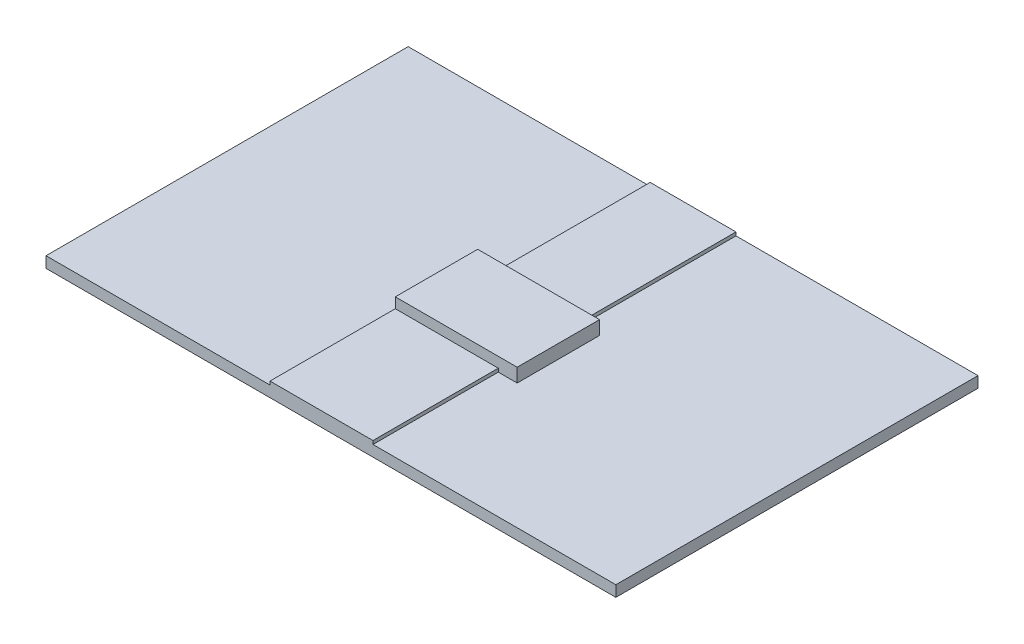
SolidWorks part; units mm, degrees
ref_plane "Front Plane" through (0, 0, 0) normal (0, 0, 1) x (1, 0, 0)
ref_plane "Top Plane" through (0, 0, 0) normal (0, 1, 0) x (1, 0, 0)
ref_plane "Right Plane" through (0, 0, 0) normal (1, 0, 0) x (0, 0, -1)
sketch "Sketch1" plane through (0, 0, 0) normal (0, 1, 0) x (1, 0, 0)
  line L1 (-83, 52.75) -> (83, 52.75)
  line L2 (-83, 52.75) -> (-83, -52.75)
  line L3 (-83, -52.75) -> (83, -52.75)
  line L4 (83, 52.75) -> (83, -52.75)
  line L5 (-83, 52.75) -> (83, -52.75) construction
  line L6 (-83, -52.75) -> (83, 52.75) construction
  line L7 (-17.75, -16.25) -> (17.75, -16.25)
  line L8 (-17.75, -16.25) -> (-17.75, 7.75)
  line L9 (-17.75, 7.75) -> (17.75, 7.75)
  line L10 (17.75, -16.25) -> (17.75, 7.75)
  line L11 (-17.75, -16.25) -> (17.75, 7.75) construction
  line L12 (-17.75, 7.75) -> (17.75, -16.25) construction
  line L13 (-17.75, -16.25) -> (12.25, -16.25)
  line L14 (-17.75, -16.25) -> (-17.75, -52.75)
  line L15 (-17.75, -52.75) -> (12.25, -52.75)
  line L16 (12.25, -16.25) -> (12.25, -52.75)
  line L17 (12.5, 7.75) -> (-12.5, 7.75)
  line L18 (12.5, 7.75) -> (12.5, 52.75)
  line L19 (12.5, 52.75) -> (-12.5, 52.75)
  line L20 (-12.5, 7.75) -> (-12.5, 52.75)
  point P0 (0, 0)
  point P5 (0, -4.25)
  dimension "D1" = 105.5
  dimension "D2" = 166
  dimension "D3" = 36.5
  dimension "D4" = 24
  dimension "D5" = 35.5
  dimension "D6" = 30
  dimension "D7" = 25
  dimension "D8" = 12.5
extrude "Boss-Extrude1" add sketch "Sketch1" along normal blind 4 contours L7 L10 L9 L8 region at (0, 0, 4.25)
extrude "Boss-Extrude2" add sketch "Sketch1<3>" against normal blind 3.2 contours L9 L20 L1 L2 L3 L14 L8 | L20 L9 L18 L1 | L16 L7 L14 L3 | L18 L9 L10 L7 L16 L3 L4 L1 | L7 L10 L9 L8 region at (-49.2054, 0, -1.0037) region at (0, 0, -30.25) region at (48.2674, 0, -0.0301) region at (0, 0, 4.25) region at (-2.75, 0, 34.5)
sketch "Sketch1<3>" plane through (0, 0, 0) normal (0, 1, 0) x (1, 0, 0) same geometry as "Sketch1"
extrude "Boss-Extrude3" add sketch "Sketch1<4>" along normal blind 1 contours L20 L9 L18 L1 | L16 L7 L14 L3 region at (0, 0, -30.25) region at (-2.75, 0, 34.5)
sketch "Sketch1<4>" plane through (0, 0, 0) normal (0, 1, 0) x (1, 0, 0) same geometry as "Sketch1"
